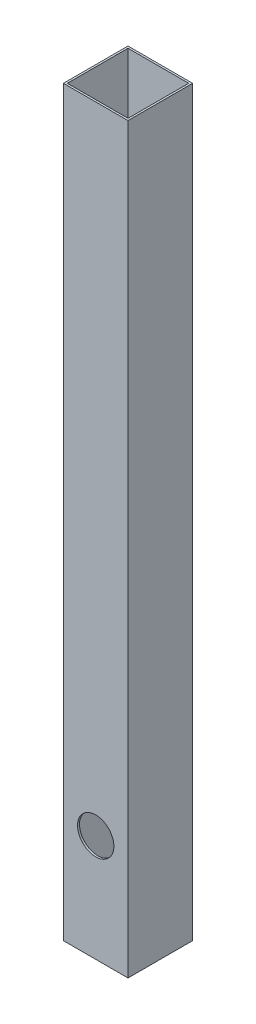
SolidWorks part; units mm, degrees
material "6061 Alloy"
ref_plane "Front Plane" through (0, 0, 0) normal (0, 0, 1) x (1, 0, 0)
ref_plane "Top Plane" through (0, 0, 0) normal (0, 1, 0) x (1, 0, 0)
ref_plane "Right Plane" through (0, 0, 0) normal (1, 0, 0) x (0, 0, -1)
sketch "Sketch1" plane through (0, 0, 0) normal (0, 1, 0) x (1, 0, 0)
  line L1 (25.4, 25.4) -> (-25.4, 25.4)
  line L2 (25.4, 25.4) -> (25.4, -25.4)
  line L3 (25.4, -25.4) -> (-25.4, -25.4)
  line L4 (-25.4, 25.4) -> (-25.4, -25.4)
  line L5 (25.4, 25.4) -> (-25.4, -25.4) construction
  line L6 (25.4, -25.4) -> (-25.4, 25.4) construction
  point P0 (0, 0)
  dimension "D1" = 50.8
extrude "Extrude-Thin1" add sketch "Sketch1" along normal blind 584.2 thin thin type one direction reverse wall 1.524
sketch "Sketch2" plane through (0, 0, 0) normal (0, 0, 1) x (1, 0, 0)
  line L0 (-36.2563, 101.6) -> (38.5702, 101.6) construction
  line L2 (-25.4, 84.1375) -> (25.4, 84.1375) construction
  line L5 (-25.4, 0) -> (25.4, 0) construction
  line L6 (25.4, 584.2) -> (25.4, 0) construction
  line L7 (-25.4, 584.2) -> (-25.4, 0) construction
  circle A0 centre (0, 84.1375) radius 14.2875
  point P6 (-25.4, 84.1375)
  point P9 (0, 84.1375)
  point P10 (0, 0)
  point P11 (0, 84.1375)
  point P14 (2.7824, 84.1375)
  point P15 (0, 0)
  dimension "D1" = 28.575
  dimension "D3" = 17.4625
  dimension "D2" = 101.6
extrude "Cut-Extrude1" cut sketch "Sketch2" along normal through all both and the other way through all
